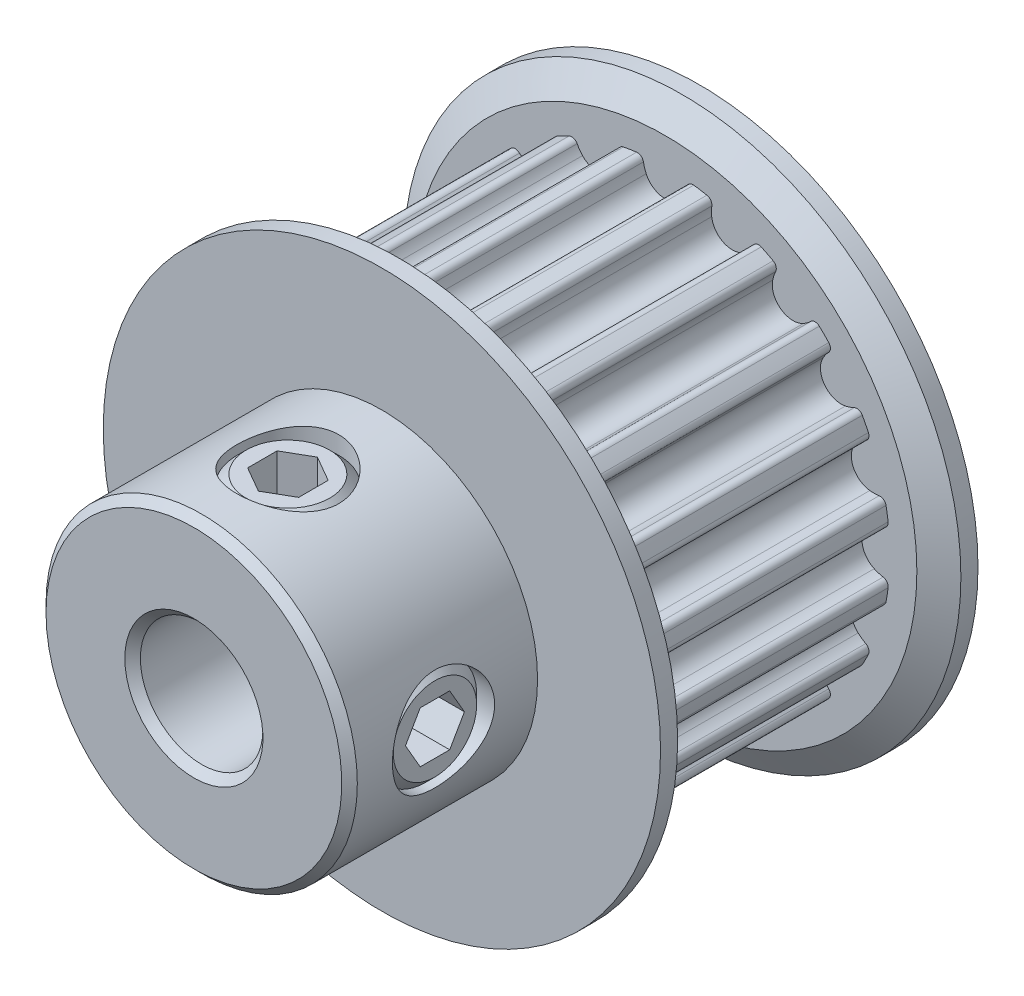
SolidWorks part; units mm, degrees
ref_plane "Front Plane" through (0, 0, 0) normal (0, 0, 1) x (1, 0, 0)
ref_plane "Top Plane" through (0, 0, 0) normal (0, 1, 0) x (1, 0, 0)
ref_plane "Right Plane" through (0, 0, 0) normal (1, 0, 0) x (0, 0, -1)
sketch "Sketch1" plane through (0, 0, 0) normal (0, 0, 1) x (1, 0, 0)
  line L1 (-2.6202, 8.0295) -> (2.6202, 8.0295) construction
  line L4 (0, 0) -> (0, 8.0295) construction
  line L5 (0, 8.0295) -> (0, 13.4291) construction
  line L6 (0, 9.5505) -> (2.9628, 9.0793) construction
  line L7 (2.9628, 9.0793) -> (4.0126, 8.7367) construction
  line L8 (2.9628, 9.0793) -> (2.6202, 8.0295) construction
  line L9 (-2.9628, 9.0793) -> (-2.6202, 8.0295) construction
  line L10 (-2.8446, 8.7171) -> (-3.7091, 11.3665)
  line L11 (-3.7091, 11.3665) -> (3.7091, 11.3665)
  line L12 (3.7091, 11.3665) -> (2.8446, 8.7171)
  circle A0 centre (0, 0) radius 9.5505 construction
  circle A1 centre (0, 0) radius 11.3665 construction
  circle A2 centre (0, 0) radius 9.1695 construction
  arc A3 (-0.7739, 8.5279) -> (0.7739, 8.5279) centre (0, 8.8795) ccw
  arc A4 (-0.7739, 8.5279) -> (-0.8866, 8.891) centre (0.61, 9.1566) cw
  arc A5 (-2.8446, 8.7171) -> (-1.1645, 9.0953) centre (0, 0) cw
  arc A6 (-0.8866, 8.891) -> (-1.1645, 9.0953) centre (-1.1328, 8.8473) ccw
  arc A7 (2.8446, 8.7171) -> (1.1645, 9.0953) centre (0, 0) ccw
  arc A8 (0.8866, 8.891) -> (1.1645, 9.0953) centre (1.1328, 8.8473) cw
  arc A9 (0.7739, 8.5279) -> (0.8866, 8.891) centre (-0.61, 9.1566) ccw
  point P6 (0, 20.9083)
  point P11 (0, 9.5505)
  point P13 (0, 11.3665)
  point P14 (0, 9.1695)
  dimension "D1" = 7.4792
  dimension "D2" = 3.8786
sketch "Sketch2" plane through (0, 0, 0) normal (1, 0, 0) x (0, 0, -1)
  line L0 (-10.31, 2.5) -> (10.31, 2.5)
  line L1 (-10.31, 2.5) -> (-10.31, 6.35)
  line L2 (-10.31, 6.35) -> (-2.64, 6.35)
  line L3 (-2.64, 6.35) -> (-2.64, 11.3665)
  line L4 (-2.64, 11.3665) -> (-1.245, 11.3665) construction
  line L5 (-1.245, 11.3665) -> (-1.245, 9.1695) construction
  line L6 (-1.245, 9.1695) -> (8.915, 9.1695)
  line L7 (8.915, 9.1695) -> (8.915, 11.3665) construction
  line L8 (8.915, 11.3665) -> (10.31, 11.3665) construction
  line L9 (10.31, 11.3665) -> (10.31, 2.5)
  line L10 (-10.31, 0) -> (10.31, 0) construction
  line L11 (9.6125, 11.3665) -> (8.915, 10.268)
  line L12 (-1.245, 10.268) -> (-1.9425, 11.3665)
  line L13 (-2.64, 11.3665) -> (-1.9425, 11.3665)
  line L14 (-1.245, 10.268) -> (-1.245, 9.1695)
  line L15 (8.915, 9.1695) -> (8.915, 10.268)
  line L16 (9.6125, 11.3665) -> (10.31, 11.3665)
  arc A0 (-1.245, 10.268) -> (-1.9425, 11.3665) centre (-2.4588, 10.268) ccw construction
  arc A1 (8.915, 10.268) -> (9.6125, 11.3665) centre (10.1288, 10.268) cw construction
  point P12 (-1.245, 10.268)
  point P14 (-1.9425, 11.3665)
  point P20 (8.915, 10.268)
  point P21 (9.6125, 11.3665)
  point P25 (8.915, 0)
  point P26 (-1.245, 0)
revolve "Revolve1" add sketch "Sketch2" angle 360 mid plane about L10
sketch "Sketch3" plane through (0, 0, 0) normal (0, 0, 1) x (1, 0, 0)
  line L6 (3.7091, 11.3665) -> (-3.7091, 11.3665)
  line L7 (2.8446, 8.7171) -> (3.7091, 11.3665)
  line L8 (-3.7091, 11.3665) -> (-2.8446, 8.7171)
  line L9 (3.7091, 11.3665) -> (-3.7091, 11.3665)
  line L10 (2.8446, 8.7171) -> (3.7091, 11.3665)
  line L11 (-3.7091, 11.3665) -> (-2.8446, 8.7171)
  arc A8 (2.8446, 8.7171) -> (1.1645, 9.0953) centre (0, 0) ccw
  arc A9 (1.1645, 9.0953) -> (0.8866, 8.891) centre (1.1328, 8.8473) ccw
  arc A10 (0.7739, 8.5279) -> (0.8866, 8.891) centre (-0.61, 9.1566) ccw
  arc A11 (-0.7739, 8.5279) -> (0.7739, 8.5279) centre (0, 8.8795) ccw
  arc A12 (-0.8866, 8.891) -> (-0.7739, 8.5279) centre (0.61, 9.1566) ccw
  arc A13 (-0.8866, 8.891) -> (-1.1645, 9.0953) centre (-1.1328, 8.8473) ccw
  arc A14 (-1.1645, 9.0953) -> (-2.8446, 8.7171) centre (0, 0) ccw
  arc A15 (2.8446, 8.7171) -> (1.1645, 9.0953) centre (0, 0) ccw
  arc A16 (1.1645, 9.0953) -> (0.8866, 8.891) centre (1.1328, 8.8473) ccw
  arc A17 (0.7739, 8.5279) -> (0.8866, 8.891) centre (-0.61, 9.1566) ccw
  arc A18 (-0.7739, 8.5279) -> (0.7739, 8.5279) centre (0, 8.8795) ccw
  arc A19 (-0.8866, 8.891) -> (-0.7739, 8.5279) centre (0.61, 9.1566) ccw
  arc A20 (-0.8866, 8.891) -> (-1.1645, 9.0953) centre (-1.1328, 8.8473) ccw
  arc A21 (-1.1645, 9.0953) -> (-2.8446, 8.7171) centre (0, 0) ccw
  dimension "D1" = 0
extrude "Cut-Extrude1" cut sketch "Sketch3" against normal up to vertex (8.915 mm away) from vertex up to point (0, 9.1695, -8.915) starting at point (0, 9.1695, 1.245)
pattern_circular "CirPattern1" count 20 over 360 about axis through (0, 0, 10.31) along (0, 0, 1) of "Cut-Extrude1"
sketch "Sketch4" plane through (0, 0, 0) normal (1, 0, 0) x (0, -1, 0)
  line L0 (0, -2.64) -> (0, -10.31) construction
  line L1 (-6.35, -2.64) -> (6.35, -2.64) construction
  line L2 (-6.35, -10.31) -> (6.35, -10.31) construction
  circle A0 centre (0, -6.475) radius 2.0828
extrude "Cut-Extrude2" cut sketch "Sketch4" along normal through all
ref_plane "Plane1" through (0, 0, 6.475) normal (0, 0, 1) x (1, 0, 0)
sketch "Sketch5" plane through (0, 0, 6.475) normal (0, 0, 1) x (1, 0, 0)
  line L0 (0, 0.1664) -> (0, 6.35) construction
  line L1 (2.5, -1.7018) -> (2.5, 0)
  line L2 (2.881, -2.0828) -> (5.6177, -2.0828)
  line L3 (2.5, 0) -> (6.35, 0) construction
  line L4 (2.5, 0) -> (5.9987, 0)
  line L5 (5.9987, 0) -> (5.9987, -1.7018)
  line L6 (2.881, -2.0828) -> (2.5, -1.7018)
  line L7 (5.9987, -1.7018) -> (5.6177, -2.0828)
  circle A0 centre (0, 0) radius 6.35 construction
  circle A1 centre (0, 0) radius 2.5 construction
  point P2 (2.5, -2.0828)
  point P11 (5.9987, -2.0828)
revolve "Revolve2" add sketch "Sketch5" angle 360 mid plane about L4
sketch "Sketch6" plane through (5.9987, 5.3841, 0) normal (-1, 0, 0) x (0, -1, 0)
  line L1 (5.3841, 7.6775) -> (4.3427, 7.0763)
  line L2 (4.3427, 7.0763) -> (4.3427, 5.8737)
  line L3 (4.3427, 5.8737) -> (5.3841, 5.2725)
  line L4 (5.3841, 5.2725) -> (6.4255, 5.8737)
  line L5 (6.4255, 5.8737) -> (6.4255, 7.0763)
  line L6 (6.4255, 7.0763) -> (5.3841, 7.6775)
  circle A0 centre (5.3841, 6.475) radius 1.0414 construction
  dimension "D1" = 2.0828
extrude "Cut-Extrude3" cut sketch "Sketch6" along normal blind 1.5621
pattern_circular "CirPattern2" count 2 over 90 about axis through (0, 0, 10.31) along (0, 0, 1) of "Cut-Extrude2", "Revolve2", "Cut-Extrude3"
chamfer "Chamfer1" distance 0.3175 angle 45 2 edges at (2.5, 0, 10.31) (6.35, 0, 10.31)
ref_axis "Center Axis 1" through (0, 0, -10.31) along (0, 0, 1)
ref_plane "Contact Plane 1" through (0, 0, 10.31) normal (0, 0, 1) x (1, 0, 0)
ref_plane "Contact Plane 2" through (0, 0, -10.31) normal (0, 0, -1) x (-1, 0, 0)
equation "\"D2@Sketch1\" = \"D1@Sketch1\"/2"
equation "\"D1@Sketch6\" = \"Set Screw@Sketch4\" / 2"
equation "\"D1@Cut-Extrude3\" = \"D1@Sketch6\"*.75"
equation "\"D1@Chamfer1\"=\"Hub Dia@Sketch2\"*.025"
